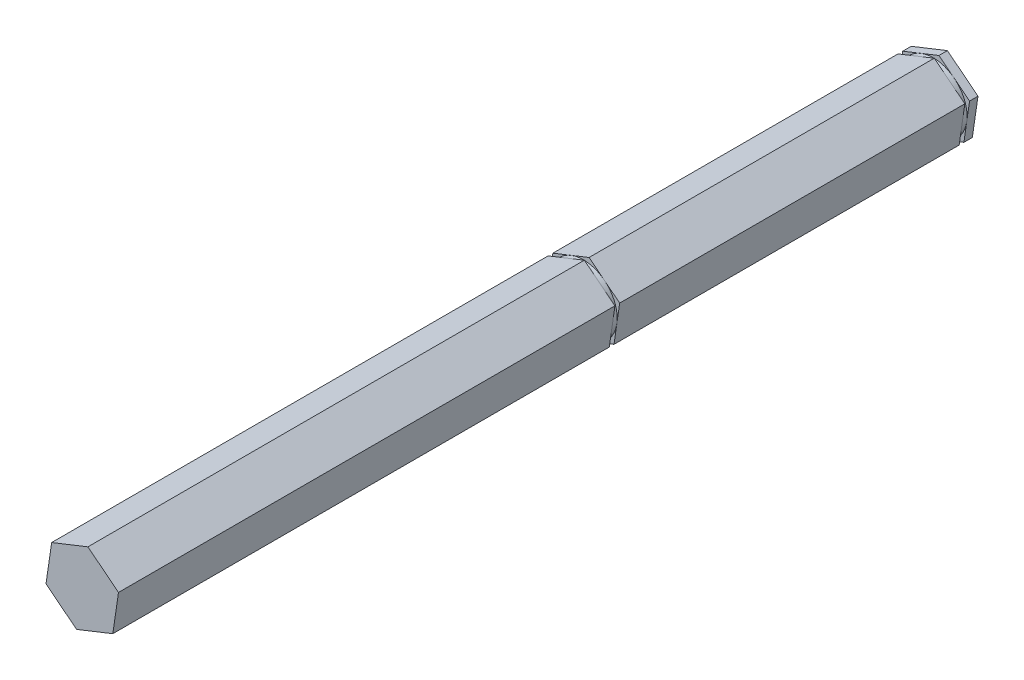
SolidWorks part; units mm, degrees
ref_plane "Front Plane" through (0, 0, 0) normal (0, 0, 1) x (1, 0, 0)
ref_plane "Top Plane" through (0, 0, 0) normal (0, 1, 0) x (1, 0, 0)
ref_plane "Right Plane" through (0, 0, 0) normal (1, 0, 0) x (0, 0, -1)
sketch "Sketch1" plane through (0, 0, 0) normal (0, 0, 1) x (1, 0, 0)
  line L1 (1.0649, 7.2546) -> (-5.7502, 4.5495)
  line L2 (-5.7502, 4.5495) -> (-6.8151, -2.7051)
  line L3 (-6.8151, -2.7051) -> (-1.0649, -7.2546)
  line L4 (-1.0649, -7.2546) -> (5.7502, -4.5495)
  line L5 (5.7502, -4.5495) -> (6.8151, 2.7051)
  line L6 (6.8151, 2.7051) -> (1.0649, 7.2546)
  circle A0 centre (0, 0) radius 6.35 construction
  dimension "D1" = 12.7
extrude "Boss-Extrude1" add sketch "Sketch1" along normal blind 161.6075
ref_plane "Plane1" through (0, 0, 68.2625) normal (0, 0, 1) x (1, 0, 0)
sketch "Sketch3" plane through (0, 0, 68.2625) normal (0, 0, 1) x (1, 0, 0)
  circle A0 centre (0, 0) radius 6.35
  circle A1 centre (0, 0) radius 7.62
  dimension "D1" = 15.24
  dimension "D2" = 12.7
extrude "Cut-Extrude1" cut sketch "Sketch3" against normal blind 0.889
ref_plane "Plane2" through (0, 0, 1.5875) normal (0, 0, -1) x (-1, 0, 0)
sketch "Sketch4" plane through (0, 0, 1.5875) normal (0, 0, -1) x (-1, 0, 0)
  circle A0 centre (0, 0) radius 6.35
  circle A1 centre (0, 0) radius 7.62
  dimension "D1" = 15.24
  dimension "D2" = 12.7
extrude "Cut-Extrude2" cut sketch "Sketch4" against normal blind 0.889
